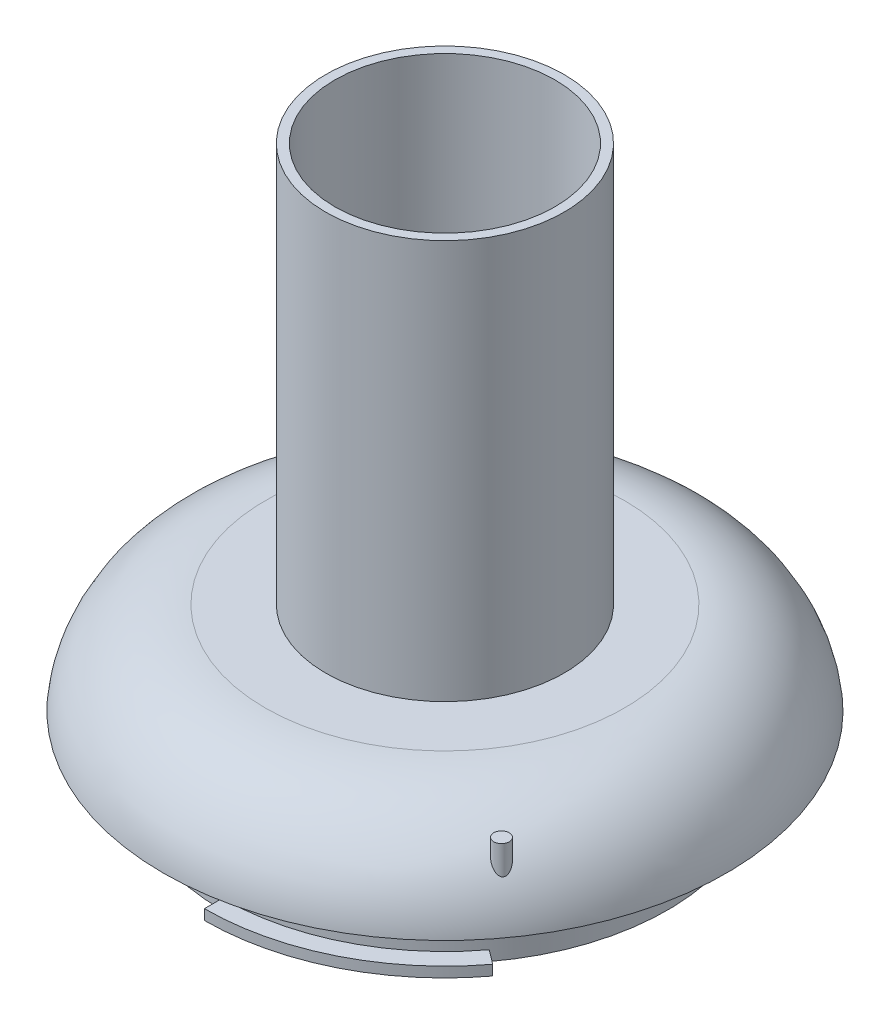
SolidWorks part; units mm, degrees
ref_plane "Front Plane" through (0, 0, 0) normal (0, 0, 1) x (1, 0, 0)
ref_plane "Top Plane" through (0, 0, 0) normal (0, 1, 0) x (1, 0, 0)
ref_plane "Right Plane" through (0, 0, 0) normal (1, 0, 0) x (0, 0, -1)
sketch "Sketch1" plane through (0, 0, 0) normal (0, 1, 0) x (1, 0, 0)
  circle A0 centre (0, 0) radius 21.75
  circle A1 centre (0, 0) radius 20
  dimension "D1" = 43.5
  dimension "D2" = 40
extrude "Boss-Extrude1" add sketch "Sketch1" along normal blind 5
sketch "Sketch2" plane through (0, 5, 0) normal (0, 1, 0) x (1, 0, 0)
  circle A0 centre (0, 0) radius 20
  circle A1 centre (0, 0) radius 23.5
  dimension "D1" = 47
extrude "Boss-Extrude2" add sketch "Sketch2" along normal blind 1
sketch "Sketch3" plane through (0, 6, 0) normal (0, 1, 0) x (1, 0, 0)
  circle A0 centre (0, 0) radius 20
  circle A1 centre (0, 0) radius 27.5
  dimension "D1" = 55
extrude "Boss-Extrude3" add sketch "Sketch3" along normal blind 8
sketch "Sketch4" plane through (0, 14, 0) normal (0, 1, 0) x (1, 0, 0)
  circle A0 centre (0, 0) radius 11.65
  circle A1 centre (0, 0) radius 10.75
  dimension "D1" = 23.3
  dimension "D2" = 21.5
extrude "Boss-Extrude4" add sketch "Sketch4" along normal blind 40 separate body
sketch "Sketch5" plane through (0, 14, 0) normal (0, 1, 0) x (1, 0, 0)
  circle A0 centre (0, 0) radius 11.65
  circle A1 centre (0, 0) radius 27.5
extrude "Boss-Extrude5" add sketch "Sketch5" along normal blind 1
sketch "Sketch6" plane through (0, 0, 0) normal (0, 0, 1) x (1, 0, 0)
  line L0 (10.75, 14) -> (20, 0)
  line L1 (-10.75, 14) -> (10.75, 14) construction
  line L2 (-20, 14) -> (20, 14) construction
  line L3 (-21.75, 0) -> (21.75, 0) construction
  line L4 (-20, 0) -> (20, 0) construction
  line L5 (20, 0) -> (20, 14)
  line L6 (20, 14) -> (10.75, 14)
  line L7 (0, 0) -> (0, 22.3381) construction
revolve "Revolve1" add sketch "Sketch6" angle 360 about L7
sketch "Sketch7" plane through (0, 0, 0) normal (0, -1, 0) x (1, 0, 0)
  line L0 (0, 21.75) -> (0, 23.5)
  line L1 (17.3882, 13.0658) -> (18.7872, 14.117)
  arc A0 (18.7872, 14.117) -> (0, 23.5) centre (0, 0) ccw
  arc A1 (17.3882, 13.0658) -> (0, 21.75) centre (0, 0) ccw
  dimension "D1" = 47
  dimension "D2" = 21
extrude "Boss-Extrude6" add sketch "Sketch7" against normal blind 1 contours A1 L0 A0 L1
pattern_circular "CirPattern1" count 3 over 360 about axis through (0, 6, 0) along (0, 1, 0) of "Boss-Extrude6", "Boss-Extrude1"
fillet "Fillet1" radius 10 1 edges at (0, 15, 27.5)
sketch "Sketch8" plane through (0, 6, 0) normal (0, -1, 0) x (1, 0, 0)
  circle A0 centre (20.4704, 14.9465) radius 0.7611
extrude "Boss-Extrude7" add sketch "Sketch8" against normal blind 7
chamfer "Chamfer2" distance 1 angle 68 1 edges at (0, 6, 23.5) first distance on face at (0, 6, 23.5)
